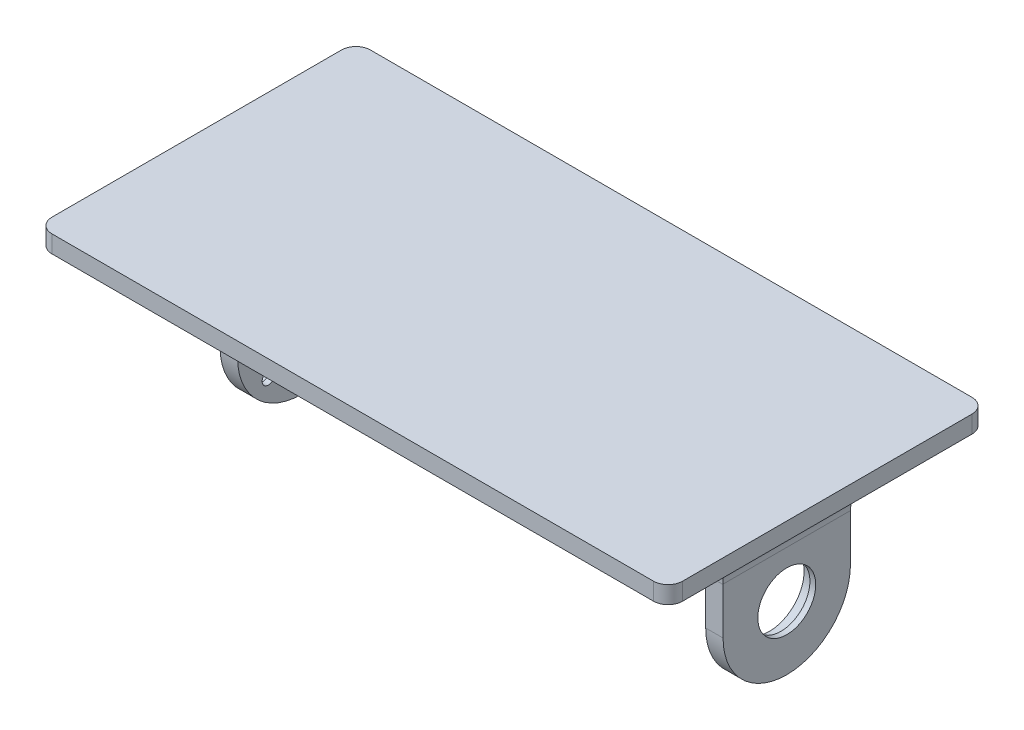
SolidWorks part; units mm, degrees
ref_plane "Front Plane" through (0, 0, 0) normal (0, 0, 1) x (1, 0, 0)
ref_plane "Top Plane" through (0, 0, 0) normal (0, 1, 0) x (1, 0, 0)
ref_plane "Right Plane" through (0, 0, 0) normal (1, 0, 0) x (0, 0, -1)
sketch "Sketch1" plane through (0, 0, 0) normal (0, 1, 0) x (1, 0, 0)
  line L5 (-40.425, 0) -> (40.425, 0) construction
  line L10 (-43.425, 11) -> (-43.425, -11)
  line L14 (43.425, 11) -> (43.425, -11)
  line L16 (-43.425, 11) -> (-40.425, 11)
  line L17 (-43.425, 11) -> (-43.425, -11)
  line L18 (-43.425, -11) -> (-40.425, -11)
  line L19 (-40.425, 11) -> (-40.425, -11)
  line L20 (43.425, 11) -> (40.425, 11)
  line L21 (43.425, 11) -> (43.425, -11)
  line L22 (43.425, -11) -> (40.425, -11)
  line L23 (40.425, 11) -> (40.425, -11)
  line L25 (-43.425, 11) -> (-43.425, -11)
  line L29 (43.425, 11) -> (43.425, -11)
  line L31 (50.425, 27.5) -> (50.425, -27.5)
  line L34 (50.425, 27.5) -> (-58.475, 27.5)
  line L35 (-58.475, -27.5) -> (-58.475, 27.5)
  line L37 (-58.475, -27.5) -> (50.425, -27.5)
  point P0 (-4.025, 0)
  point P5 (0, 0)
  point P15 (-4.025, -27.5)
  point P17 (50.425, 0)
  point P29 (-40.425, 0)
  point P30 (40.425, 0)
  dimension "D5" = 7
  dimension "D1" = 86.85
  dimension "D2" = 55
  dimension "D3" = 3
  dimension "D4" = 22
  dimension "D6" = 108.9
extrude "Boss-Extrude1" add sketch "Sketch1" along normal blind 3 contours L34 L35 L37 L31
sketch "Sketch5" plane through (0, 0, 0) normal (0, -1, 0) x (1, 0, 0)
  line L1 (-43.425, 11) -> (-40.425, 11)
  line L2 (-43.425, 11) -> (-43.425, -11)
  line L3 (-43.425, -11) -> (-40.425, -11)
  line L4 (-40.425, 11) -> (-40.425, -11)
  line L5 (40.425, 11) -> (43.425, 11)
  line L6 (40.425, 11) -> (40.425, -11)
  line L7 (40.425, -11) -> (43.425, -11)
  line L8 (43.425, 11) -> (43.425, -11)
  dimension "D2" = 3
extrude "Boss-Extrude2" add sketch "Sketch5" along normal blind 27
sketch "Sketch2" plane through (-43.425, 0, 0) normal (-1, 0, 0) x (0, 0, 1)
  line L0 (0, -16) -> (-5.6569, -21.6569) construction
  line L2 (11, -27) -> (-11, -27) construction
  circle A2 centre (0, -16) radius 3
  circle A3 centre (-5.6569, -21.6569) radius 1.1
  dimension "D1" = 8
  dimension "D5" = 11
  dimension "D2" = 6
  dimension "D3" = 2.2
  dimension "D4" = 45
extrude "Cut-Extrude1" cut sketch "Sketch2" against normal up to surface (3 mm away) contours A2 | A3 region at (-43.425, -16, 0) up to face at (-40.425, -13.5, 0)
pattern_circular "CirPattern1" count 4 over 360 about axis through (-43.425, -16, 0) along (-1, 0, 0) of "Cut-Extrude1"
fillet "Fillet3" radius 11 4 edges at (-41.925, -27, -11) (-41.925, -27, 11) (41.925, -27, -11) (41.925, -27, 11)
sketch "Sketch6" plane through (-43.425, 0, 0) normal (-1, 0, 0) x (0, 0, 1)
  circle A0 centre (5.6569, -10.3431) radius 2
  circle A1 centre (5.6569, -10.3431) radius 1.1 construction
  dimension "D1" = 4
extrude "Cut-Extrude5" cut sketch "Sketch6" against normal offset from surface (2 mm away) 1 up to face at (-40.425, -10.3431, -4.5569)
pattern_circular "CirPattern2" count 4 over 360 about axis through (-43.425, -16, 0) along (-1, 0, 0) of "Cut-Extrude5"
sketch "Sketch7" plane through (40.425, 0, 0) normal (-1, 0, 0) x (0, 0, 1)
  circle A1 centre (0, -16) radius 3 construction
  circle A2 centre (0, -16) radius 5
  circle A3 centre (0, -16) radius 6
  dimension "D2" = 12
  dimension "D3" = 1
extrude "Cut-Extrude6" cut sketch "Sketch7" against normal up to surface (10 mm away) contours A2 region at (40.425, -16, 0) up to face at (50.425, 1.5, 0)
extrude "Cut-Extrude7" cut sketch "Sketch7<5>" against normal offset from surface (2 mm away) 1 up to face at (43.425, -16, 5)
sketch "Sketch7<5>" plane through (40.425, 0, 0) normal (-1, 0, 0) x (0, 0, 1) same geometry as "Sketch7"
fillet "Fillet4" radius 8 8 edges at (-43.425, 0, 0) (40.425, 0, 0) (-40.425, 0, 0) (41.925, 0, 11) (41.925, 0, -11) (-41.925, 0, 11) (-41.925, 0, -11) (43.425, 0, 0)
fillet "Filete1" radius 2.5 4 edges at (50.425, 1.5, 27.5) (50.425, 1.5, -27.5) (-58.475, 1.5, 27.5) (-58.475, 1.5, -27.5)
move or copy body "Corpo-Mover/Copiar1" [suppressed]
